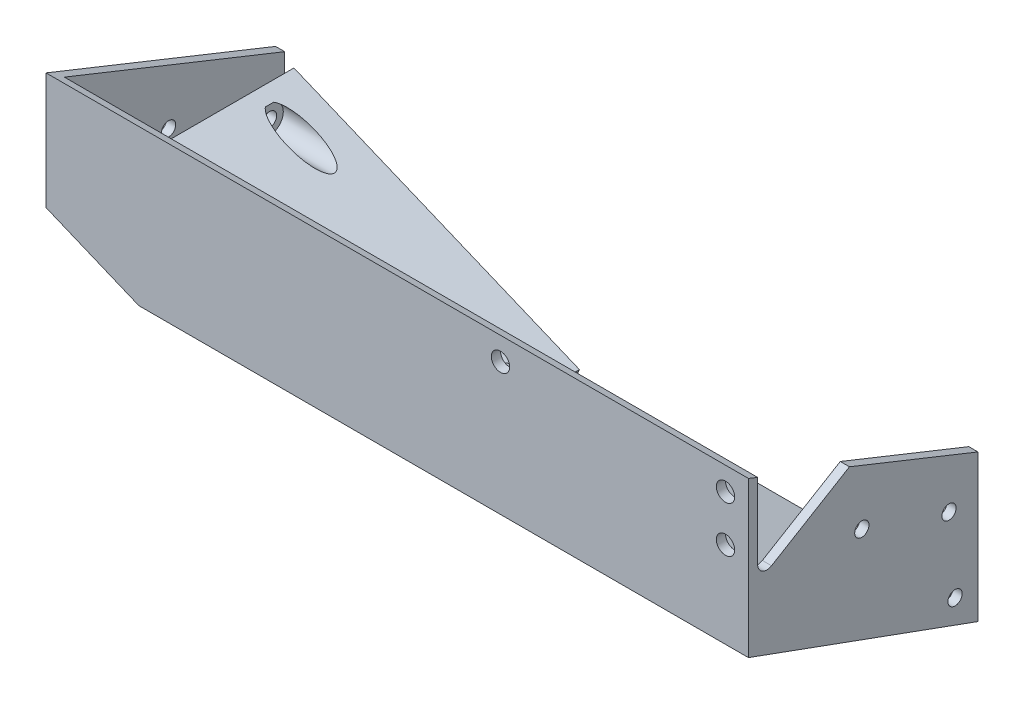
SolidWorks part; units mm, degrees
material "聚脂树脂"
ref_plane "前视基准面" through (0, 0, 0) normal (0, 0, 1) x (1, 0, 0)
ref_plane "上视基准面" through (0, 0, 0) normal (0, 1, 0) x (1, 0, 0)
ref_plane "右视基准面" through (0, 0, 0) normal (1, 0, 0) x (0, 0, -1)
sketch "Sketch1" plane through (0, 0, 0) normal (0, 0, 1) x (1, 0, 0)
  line L1 (-76.5, 26) -> (76.5, 26)
  line L2 (-76.5, 26) -> (-76.5, -26)
  line L3 (-76.5, -26) -> (76.5, -26)
  line L4 (76.5, 26) -> (76.5, -26)
  line L5 (-76.5, 26) -> (76.5, -26) construction
  line L6 (-76.5, -26) -> (76.5, 26) construction
  point P0 (0, 0)
  dimension "D1" = 153
  dimension "D2" = 52
extrude "Boss-Extrude1" add sketch "Sketch1" along normal blind 50
sketch "Sketch2" plane through (-76.5, 0, 0) normal (-1, 0, 0) x (0, 0, 1)
  line L0 (0, -26) -> (50, -7.8015)
  line L1 (50, -26) -> (0, -26) construction
  line L2 (50, 26) -> (50, -26) construction
  line L3 (50, -7.8015) -> (50, -26)
  line L4 (50, -26) -> (0, -26)
  dimension "D1" = 20
extrude "Cut-Extrude1" cut sketch "Sketch2" against normal through all both and the other way through all
sketch "Sketch3" plane through (0, 0, 0) normal (0, 0, -1) x (-1, 0, 0)
  line L0 (76.5, 0.5917) -> (12.3984, -26)
  line L1 (76.5, 26) -> (76.5, -26) construction
  line L2 (76.5, -26) -> (-76.5, -26) construction
  line L3 (12.3984, -26) -> (76.5, -26)
  line L4 (76.5, -26) -> (76.5, 0.5917)
extrude "Cut-Extrude2" cut sketch "Sketch3" against normal through all both and the other way through all
shell "Shell1" thickness 2 removed face at (0, 26, 25) removed face at (-4.9594, 0, 0)
sketch "Sketch4" plane through (-10.2562, -24.7234, 0) normal (0.3832, 0.9237, 0) x (0.9237, -0.3832, 0)
  line L0 (-2.2229, 0) -> (-2.2229, 2)
  line L1 (-2.2229, 0) -> (-69.5523, 0) construction
  line L2 (-47.8172, -48) -> (-2.2229, 0) construction
  line L3 (-2.2229, 2) -> (-69.5523, 2)
  line L4 (-69.5523, 2) -> (-69.5523, 0)
  line L5 (-69.5523, -48) -> (-69.5523, 0) construction
  line L6 (-78.7764, 0) -> (-69.5523, 0) construction
  line L7 (-69.5523, 0) -> (-2.2229, 0)
  dimension "D1" = 2
extrude "Boss-Extrude2" add sketch "Sketch4" against normal up to surface (2 mm away) up to face at (-52.8874, -9.2037, 31.25)
sketch "Sketch5" plane through (-11.0225, -26.5708, 0) normal (-0.3832, -0.9237, 0) x (0.9237, -0.3832, 0)
  line L0 (-41.8879, -2) -> (-41.8879, 1)
  line L1 (-69.5523, -2) -> (-2.2229, -2) construction
  line L2 (-41.8879, 1) -> (-3.8879, 1)
  line L3 (-3.8879, 1) -> (-3.8879, -2)
  line L4 (-3.8879, -2) -> (-41.8879, -2)
  dimension "D1" = 3
  dimension "D2" = 38
extrude "Boss-Extrude3" add sketch "Sketch5" along normal blind 6
sketch "Sketch6" plane through (0, 0, -2) normal (0, 0, -1) x (-1, 0, 0)
  circle A0 centre (37.0078, -19.039) radius 1.55
  circle A1 centre (18.5343, -26.7025) radius 1.55
extrude "Cut-Extrude3" cut sketch "Sketch6" against normal blind 6
sketch "Sketch8" plane through (-76.5, 0, 0) normal (-1, 0, 0) x (0, 0, 1)
  circle A0 centre (6.3167, -2.178) radius 4
  dimension "D1" = 8
extrude "Boss-Extrude4" add sketch "Sketch8" against normal up to surface (6.6765 mm away) up to face at (-45.6653, -12.1997, 9.9167)
sketch "Sketch9" plane through (-76.5, 0, 0) normal (-1, 0, 0) x (0, 0, 1)
  circle A0 centre (25.306, 4.0994) radius 1.55
  circle A1 centre (6.3167, -2.178) radius 1.55
extrude "Cut-Extrude4" cut sketch "Sketch9" against normal blind 66
sketch "Sketch10" plane through (76.5, 0, 0) normal (1, 0, 0) x (0, 0, -1)
  circle A0 centre (-5, -19) radius 1.55
  circle A1 centre (-6.3167, -2.178) radius 1.55
  circle A2 centre (-25.306, 4.0994) radius 1.55
extrude "Cut-Extrude5" cut sketch "Sketch10" against normal blind 66
sketch "Sketch11" plane through (0, 0, 48) normal (0, 0, -1) x (-1, 0, 0)
  circle A0 centre (-71.5, 11) radius 2
  circle A1 centre (-71.5, 21) radius 2
  circle A2 centre (-22.5, 21) radius 2
extrude "Cut-Extrude6" cut sketch "Sketch11" against normal blind 66
sketch "Sketch12" plane through (-76.5, 0, 0) normal (-1, 0, 0) x (0, 0, 1)
  circle A0 centre (6.3167, -2.178) radius 3
  dimension "D1" = 6
extrude "Cut-Extrude7" cut sketch "Sketch12" along normal blind 146 from surface starting at face at (74.5, -20.55, 5)
sketch "Sketch13" plane through (76.5, 0, 0) normal (1, 0, 0) x (0, 0, -1)
  line L0 (0, 6) -> (-50, 26)
  line L1 (0, -26) -> (0, 26) construction
  line L2 (-50, 26) -> (0, 26)
  line L3 (0, 26) -> (0, 6)
  dimension "D1" = 20
extrude "Cut-Extrude8" cut sketch "Sketch13" against normal through all both and the other way through all
sketch "Sketch14" plane through (74.5, 0, 0) normal (-1, 0, 0) x (0, 0, 1)
  line L1 (48, 5.2) -> (48, 25.2)
  line L2 (48, -6.4011) -> (48, 25.2) construction
  line L3 (48, 25.2) -> (28, 17.2)
  line L4 (0, 6) -> (48, 25.2) construction
  line L5 (28, 17.2) -> (48, 5.2)
  dimension "D1" = 20
  dimension "D2" = 20
extrude "Cut-Extrude9" cut sketch "Sketch14" against normal blind 146
fillet "Fillet1" radius 2 1 edges at (75.5, 5.2, 48)
sketch "Sketch15" plane through (0, -21.0792, 7.6722) normal (0, 0.9397, -0.342) x (1, 0, 0)
  circle A0 centre (63.355, -2.3989) radius 1
  circle A1 centre (63.355, -20.3989) radius 1
  circle A2 centre (18.155, -20.3989) radius 1
  circle A3 centre (18.155, -2.3989) radius 1
  circle A4 centre (2.1968, -17.717) radius 1
  circle A5 centre (2.1968, -35.717) radius 1
  circle A6 centre (-43.0032, -35.717) radius 1
extrude "Cut-Extrude10" cut sketch "Sketch15" against normal blind 146
